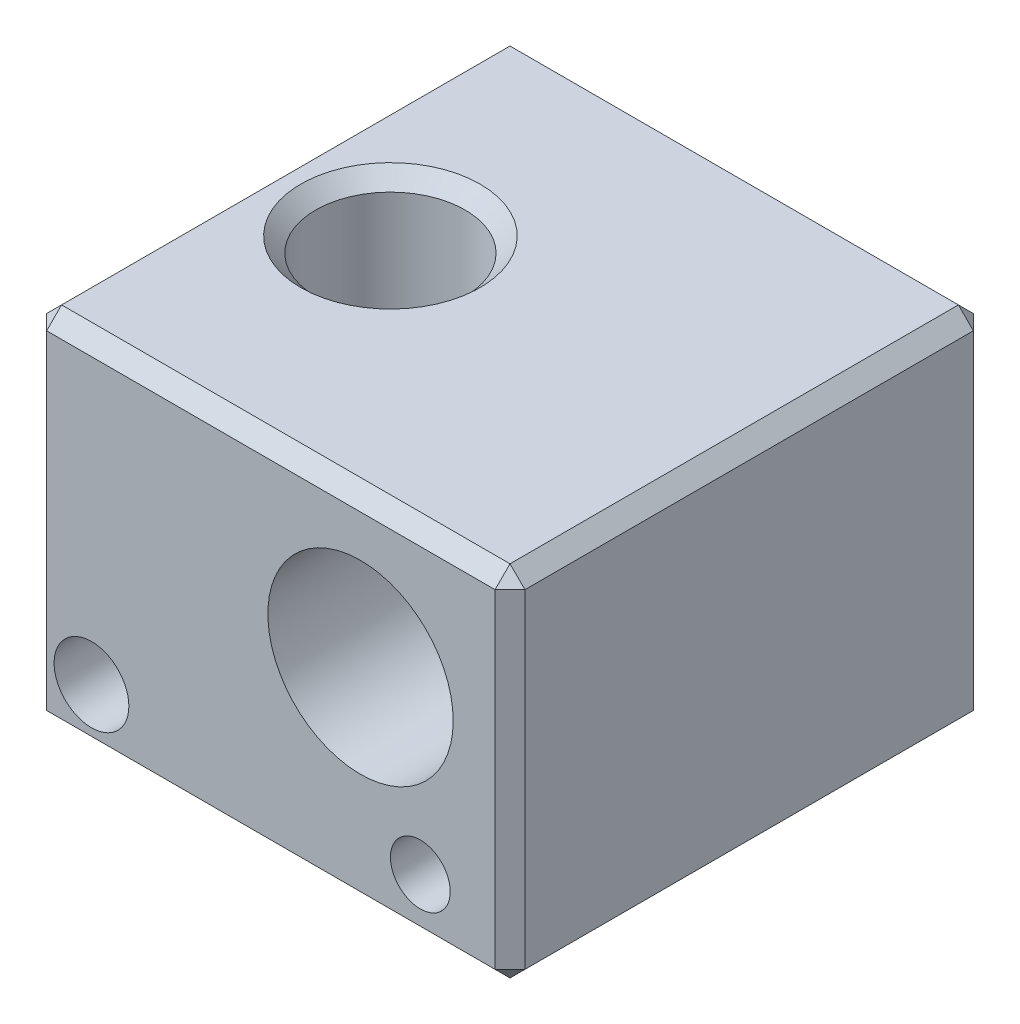
SolidWorks part; units mm, degrees
material "AISI 316 Annealed Stainless Steel Bar (SS)"
ref_plane "Front Plane" through (0, 0, 0) normal (0, 0, 1) x (1, 0, 0)
ref_plane "Top Plane" through (0, 0, 0) normal (0, 1, 0) x (1, 0, 0)
ref_plane "Right Plane" through (0, 0, 0) normal (1, 0, 0) x (0, 0, -1)
sketch "Sketch1" plane through (0, 0, 0) normal (0, 1, 0) x (1, 0, 0)
  line L1 (-8, -8) -> (8, -8)
  line L2 (-8, -8) -> (-8, 8)
  line L3 (-8, 8) -> (8, 8)
  line L4 (8, -8) -> (8, 8)
  line L5 (-8, -8) -> (8, 8) construction
  line L6 (-8, 8) -> (8, -8) construction
  point P0 (0, 0)
  dimension "D1" = 16
  dimension "D2" = 16
extrude "Boss-Extrude1" add sketch "Sketch1" along normal blind 12 contours L2 L3 L4 L1
sketch "Sketch2" plane through (0, 0, 8) normal (0, 0, 1) x (1, 0, 0)
  line L0 (-8, 12) -> (-8, 0) construction
  line L1 (-8, 0) -> (8, 0) construction
  circle A0 centre (3, 7) radius 3.1
  circle A1 centre (5, 2) radius 1
  dimension "D2" = 6.2
  dimension "D4" = 13
  dimension "D6" = 2
  dimension "D1" = 11
  dimension "D3" = 7
  dimension "D5" = 2
extrude "Cut-Extrude1" cut sketch "Sketch2" against normal through all
hole_wizard "Ø2.5 (2.5) Diameter Hole1" positions "Sketch4" profile "Sketch3" hole size "Ø2.5" standard "ANSI Metric"
sketch "Sketch4" plane through (0, 0, 8) normal (0, 0, 1) x (1, 0, 0)
  line L0 (-8, 12) -> (-8, 0) construction
  line L1 (-8, 0) -> (8, 0) construction
  point P0 (-6, 2)
  dimension "D1" = 2
  dimension "D2" = 2
sketch "Sketch3" plane through (-6, 2, 8) normal (1, 0, 0) x (0, -1, 0)
  line L0 (0, 0) -> (0, 4.5)
  line L1 (0, 4.5) -> (1.25, 4.5)
  line L2 (1.25, 4.5) -> (1.25, 0)
  line L5 (1.25, 0) -> (0, 0)
  line L10 (0, 4.5) -> (-1.25, 4.5) construction
  line L11 (0, -6.35) -> (0, 107.95) construction
  dimension "Hole Dia." = 2.5
  dimension "Hole Depth" = 4.5
  dimension "Drill Angle" = 180
hole_wizard "Tap Drill for M6x1.0 Tap1" positions "Sketch7" profile "Sketch6" hole size "M6x1.0" standard "ANSI Metric" end condition through all
sketch "Sketch7" plane through (0, 12, 0) normal (0, 1, 0) x (1, 0, 0)
  line L0 (-8, -8) -> (-8, 8) construction
  point P0 (-4, 0)
  dimension "D1" = 4
sketch "Sketch6" plane through (-4, 12, 0) normal (1, 0, 0) x (0, 0, 1)
  line L0 (0, 0) -> (0, 12)
  line L1 (0, 12) -> (2.5, 12)
  line L2 (2.5, 12) -> (2.5, 0)
  line L5 (2.5, 0) -> (0, 0)
  line L11 (0, -6.35) -> (0, 107.95) construction
  dimension "Thru Hole Dia." = 5
  dimension "Thru Hole Depth" = 12
hole_wizard "Tap Drill for M3x0.5 Tap1" positions "Sketch9" profile "Sketch8" hole size "M3x0.5" standard "ANSI Metric"
sketch "Sketch9" plane through (0, 0, 0) normal (0, -1, 0) x (-1, 0, 0)
  line L0 (8, -8) -> (8, 8) construction
  point P0 (-2, 0)
  dimension "D1" = 10
sketch "Sketch8" plane through (2, 0, 0) normal (1, 0, 0) x (0, 0, -1)
  line L0 (0, 0) -> (0, 7.7501)
  line L1 (0, 7.7501) -> (1.25, 6.999)
  line L2 (1.25, 6.999) -> (1.25, 0)
  line L5 (1.25, 0) -> (0, 0)
  line L10 (0, 7.7501) -> (-1.25, 6.999) construction
  line L11 (0, -6.35) -> (0, 107.95) construction
  dimension "Hole Dia." = 2.5
  dimension "Hole Depth" = 6.999
  dimension "Drill Angle" = 118
chamfer "Chamfer1" distance 0.5 angle 45 15 edges at (-4, 0, 2.5) (2, 0, -1.25) (-8, 6, -8) (-8, 6, 8) (8, 6, 8) (8, 0, 0) (0, 0, 8) (-8, 0, 0) (0, 0, -8) (8, 6, -8) (-8, 12, 0) (0, 12, -8) (8, 12, 0) (0, 12, 8) (-4, 12, 2.5)
